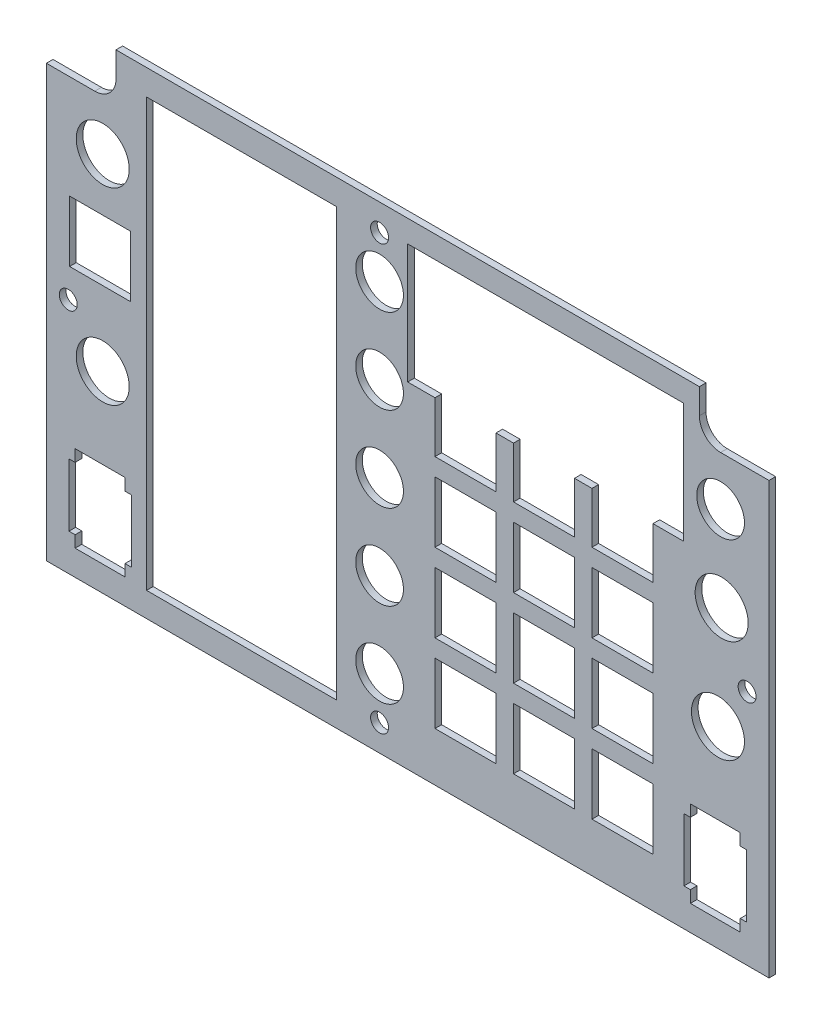
SolidWorks part; units mm, degrees
material "ABS PC"
ref_plane "Front Plane" through (0, 0, 0) normal (0, 0, 1) x (1, 0, 0)
ref_plane "Top Plane" through (0, 0, 0) normal (0, 1, 0) x (1, 0, 0)
ref_plane "Right Plane" through (0, 0, 0) normal (1, 0, 0) x (0, 0, -1)
sketch "Sketch1" plane through (0, 0, 0) normal (0, 0, 1) x (1, 0, 0)
  line L8 (58.2068, 169.534) -> (58.2068, 175.5665)
  line L9 (58.2068, 175.5665) -> (-81.4932, 175.5665)
  line L10 (-81.4932, 175.5665) -> (-81.4932, 169.534)
  line L11 (-86.5732, 164.454) -> (-98.162, 164.454)
  line L12 (-98.162, 164.454) -> (-98.162, 61.2665)
  line L13 (-98.162, 61.2665) -> (74.8755, 61.2665)
  line L14 (74.8755, 61.2665) -> (74.8755, 164.454)
  line L15 (74.8755, 164.454) -> (63.2868, 164.454)
  line L16 (58.2068, 169.534) -> (58.2068, 175.5665)
  line L17 (58.2068, 175.5665) -> (-81.4932, 175.5665)
  line L18 (-81.4932, 175.5665) -> (-81.4932, 169.534)
  line L19 (-86.5732, 164.454) -> (-98.162, 164.454)
  line L20 (-98.162, 164.454) -> (-98.162, 61.2665)
  line L21 (-98.162, 61.2665) -> (74.8755, 61.2665)
  line L22 (74.8755, 61.2665) -> (74.8755, 164.454)
  line L23 (74.8755, 164.454) -> (63.2868, 164.454)
  arc A2 (58.2068, 169.534) -> (63.2868, 164.454) centre (63.2868, 169.534) ccw
  arc A3 (-86.5732, 164.454) -> (-81.4932, 169.534) centre (-86.5732, 169.534) ccw
  arc A4 (58.2068, 169.534) -> (63.2868, 164.454) centre (63.2868, 169.534) ccw
  arc A5 (-86.5732, 164.454) -> (-81.4932, 169.534) centre (-86.5732, 169.534) ccw
  dimension "D1" = 0
extrude "Boss-Extrude1" add sketch "Sketch1" along normal blind 1.5875
sketch "Sketch2" plane through (0, 0, 1.5875) normal (0, 0, 1) x (1, 0, 0)
  line L4 (67.9868, 85.1738) -> (67.9868, 87.9695)
  line L5 (56.0468, 67.3295) -> (67.9868, 67.3295)
  line L6 (56.0468, 70.1738) -> (56.0468, 67.3295)
  line L7 (67.9868, 87.9695) -> (56.0468, 87.9695)
  line L8 (67.9868, 85.1738) -> (67.9868, 87.9695)
  line L9 (56.0468, 67.3295) -> (67.9868, 67.3295)
  line L10 (56.0468, 70.1738) -> (56.0468, 67.3295)
  line L11 (67.9868, 87.9695) -> (56.0468, 87.9695)
  line L26 (32.4893, 73.014) -> (47.0943, 73.014)
  line L27 (32.4893, 87.619) -> (32.4893, 73.014)
  line L28 (47.0943, 87.619) -> (32.4893, 87.619)
  line L29 (47.0943, 73.014) -> (47.0943, 87.619)
  line L30 (32.4893, 73.014) -> (47.0943, 73.014)
  line L31 (32.4893, 87.619) -> (32.4893, 73.014)
  line L32 (47.0943, 87.619) -> (32.4893, 87.619)
  line L33 (47.0943, 73.014) -> (47.0943, 87.619)
  line L34 (32.4893, 91.81) -> (47.0943, 91.81)
  line L35 (32.4893, 106.415) -> (32.4893, 91.81)
  line L36 (47.0943, 106.415) -> (32.4893, 106.415)
  line L37 (47.0943, 91.81) -> (47.0943, 106.415)
  line L38 (32.4893, 91.81) -> (47.0943, 91.81)
  line L39 (32.4893, 106.415) -> (32.4893, 91.81)
  line L40 (47.0943, 106.415) -> (32.4893, 106.415)
  line L41 (47.0943, 91.81) -> (47.0943, 106.415)
  line L42 (32.4893, 110.606) -> (47.0943, 110.606)
  line L43 (32.4893, 125.211) -> (32.4893, 110.606)
  line L44 (47.0943, 125.211) -> (32.4893, 125.211)
  line L45 (47.0943, 110.606) -> (47.0943, 125.211)
  line L46 (32.4893, 110.606) -> (47.0943, 110.606)
  line L47 (32.4893, 125.211) -> (32.4893, 110.606)
  line L48 (47.0943, 125.211) -> (32.4893, 125.211)
  line L49 (47.0943, 110.606) -> (47.0943, 125.211)
  line L51 (13.6933, 73.014) -> (28.2983, 73.014)
  line L52 (13.6933, 87.619) -> (13.6933, 73.014)
  line L53 (28.2983, 87.619) -> (13.6933, 87.619)
  line L54 (28.2983, 73.014) -> (28.2983, 87.619)
  line L55 (13.6933, 73.014) -> (28.2983, 73.014)
  line L56 (13.6933, 87.619) -> (13.6933, 73.014)
  line L57 (28.2983, 87.619) -> (13.6933, 87.619)
  line L58 (28.2983, 73.014) -> (28.2983, 87.619)
  line L59 (13.6933, 91.81) -> (28.2983, 91.81)
  line L60 (13.6933, 106.415) -> (13.6933, 91.81)
  line L61 (28.2983, 106.415) -> (13.6933, 106.415)
  line L62 (32.4893, 141.6095) -> (32.4893, 129.402)
  line L63 (28.2983, 141.6095) -> (32.4893, 141.6095)
  line L64 (28.2983, 129.402) -> (28.2983, 141.6095)
  line L65 (13.6933, 129.402) -> (28.2983, 129.402)
  line L66 (13.6933, 141.6095) -> (13.6933, 129.402)
  line L67 (9.5023, 141.6095) -> (13.6933, 141.6095)
  line L68 (9.5023, 129.402) -> (9.5023, 141.6095)
  line L69 (-5.1027, 129.402) -> (9.5023, 129.402)
  line L70 (-5.1027, 141.6095) -> (-5.1027, 129.402)
  line L71 (-11.6432, 141.6095) -> (-5.1027, 141.6095)
  line L72 (-11.6432, 170.2495) -> (-11.6432, 141.6095)
  line L73 (54.3968, 170.2495) -> (-11.6432, 170.2495)
  line L74 (54.3968, 141.6095) -> (54.3968, 170.2495)
  line L75 (47.0943, 141.6095) -> (54.3968, 141.6095)
  line L76 (47.0943, 129.402) -> (47.0943, 141.6095)
  line L77 (32.4893, 129.402) -> (47.0943, 129.402)
  line L78 (32.4893, 141.6095) -> (32.4893, 129.402)
  line L79 (28.2983, 141.6095) -> (32.4893, 141.6095)
  line L80 (28.2983, 129.402) -> (28.2983, 141.6095)
  line L81 (13.6933, 129.402) -> (28.2983, 129.402)
  line L82 (13.6933, 141.6095) -> (13.6933, 129.402)
  line L83 (9.5023, 141.6095) -> (13.6933, 141.6095)
  line L84 (9.5023, 129.402) -> (9.5023, 141.6095)
  line L85 (-5.1027, 129.402) -> (9.5023, 129.402)
  line L86 (-5.1027, 141.6095) -> (-5.1027, 129.402)
  line L87 (-11.6432, 141.6095) -> (-5.1027, 141.6095)
  line L88 (-11.6432, 170.2495) -> (-11.6432, 141.6095)
  line L89 (54.3968, 170.2495) -> (-11.6432, 170.2495)
  line L90 (54.3968, 141.6095) -> (54.3968, 170.2495)
  line L91 (47.0943, 141.6095) -> (54.3968, 141.6095)
  line L92 (47.0943, 129.402) -> (47.0943, 141.6095)
  line L93 (32.4893, 129.402) -> (47.0943, 129.402)
  line L94 (28.2983, 91.81) -> (28.2983, 106.415)
  line L95 (13.6933, 91.81) -> (28.2983, 91.81)
  line L96 (13.6933, 106.415) -> (13.6933, 91.81)
  line L97 (28.2983, 106.415) -> (13.6933, 106.415)
  line L98 (28.2983, 91.81) -> (28.2983, 106.415)
  line L99 (13.6933, 110.606) -> (28.2983, 110.606)
  line L100 (13.6933, 125.211) -> (13.6933, 110.606)
  line L101 (28.2983, 125.211) -> (13.6933, 125.211)
  line L102 (28.2983, 110.606) -> (28.2983, 125.211)
  line L103 (13.6933, 110.606) -> (28.2983, 110.606)
  line L104 (13.6933, 125.211) -> (13.6933, 110.606)
  line L105 (28.2983, 125.211) -> (13.6933, 125.211)
  line L106 (28.2983, 110.606) -> (28.2983, 125.211)
  line L107 (9.5023, 125.211) -> (-5.1027, 125.211)
  line L108 (9.5023, 110.606) -> (9.5023, 125.211)
  line L109 (-5.1027, 110.606) -> (9.5023, 110.606)
  line L110 (-5.1027, 125.211) -> (-5.1027, 110.606)
  line L111 (9.5023, 125.211) -> (-5.1027, 125.211)
  line L112 (9.5023, 110.606) -> (9.5023, 125.211)
  line L113 (-5.1027, 110.606) -> (9.5023, 110.606)
  line L114 (-5.1027, 125.211) -> (-5.1027, 110.606)
  line L115 (-5.1027, 91.81) -> (9.5023, 91.81)
  line L116 (-5.1027, 106.415) -> (-5.1027, 91.81)
  line L117 (9.5023, 106.415) -> (-5.1027, 106.415)
  line L118 (9.5023, 91.81) -> (9.5023, 106.415)
  line L119 (-5.1027, 91.81) -> (9.5023, 91.81)
  line L120 (-5.1027, 106.415) -> (-5.1027, 91.81)
  line L121 (9.5023, 106.415) -> (-5.1027, 106.415)
  line L122 (9.5023, 91.81) -> (9.5023, 106.415)
  line L123 (-5.1027, 73.014) -> (9.5023, 73.014)
  line L124 (-5.1027, 87.619) -> (-5.1027, 73.014)
  line L125 (9.5023, 87.619) -> (-5.1027, 87.619)
  line L126 (9.5023, 73.014) -> (9.5023, 87.619)
  line L127 (-5.1027, 73.014) -> (9.5023, 73.014)
  line L128 (-5.1027, 87.619) -> (-5.1027, 73.014)
  line L129 (9.5023, 87.619) -> (-5.1027, 87.619)
  line L130 (9.5023, 73.014) -> (9.5023, 87.619)
  line L131 (-78.0007, 139.689) -> (-92.6057, 139.689)
  line L132 (-78.0007, 125.084) -> (-78.0007, 139.689)
  line L133 (-92.6057, 125.084) -> (-78.0007, 125.084)
  line L134 (-92.6057, 139.689) -> (-92.6057, 125.084)
  line L135 (-78.0007, 139.689) -> (-92.6057, 139.689)
  line L136 (-78.0007, 125.084) -> (-78.0007, 139.689)
  line L137 (-92.6057, 125.084) -> (-78.0007, 125.084)
  line L138 (-92.6057, 139.689) -> (-92.6057, 125.084)
  line L139 (-74.1732, 67.1295) -> (-28.7112, 67.1295)
  line L140 (-74.1732, 169.4495) -> (-74.1732, 67.1295)
  line L141 (-28.7112, 169.4495) -> (-74.1732, 169.4495)
  line L142 (-28.7112, 67.1295) -> (-28.7112, 169.4495)
  line L143 (-74.1732, 67.1295) -> (-28.7112, 67.1295)
  line L144 (-74.1732, 169.4495) -> (-74.1732, 67.1295)
  line L145 (-28.7112, 169.4495) -> (-74.1732, 169.4495)
  line L146 (-28.7112, 67.1295) -> (-28.7112, 169.4495)
  line L147 (-79.3332, 85.1165) -> (-79.3332, 87.9695)
  line L148 (-91.2732, 67.3295) -> (-79.3332, 67.3295)
  line L149 (-91.2732, 70.1165) -> (-91.2732, 67.3295)
  line L150 (-79.3332, 87.9695) -> (-91.2732, 87.9695)
  line L151 (-79.3332, 85.1165) -> (-79.3332, 87.9695)
  line L152 (-91.2732, 67.3295) -> (-79.3332, 67.3295)
  line L153 (-91.2732, 70.1165) -> (-91.2732, 67.3295)
  line L154 (-79.3332, 87.9695) -> (-91.2732, 87.9695)
  line L176 (54.505, 85.1738) -> (54.505, 70.1738)
  line L177 (54.505, 85.1738) -> (54.505, 70.1738)
  line L178 (56.0468, 85.1738) -> (54.505, 85.1738)
  line L179 (56.0468, 85.1738) -> (54.505, 85.1738)
  line L180 (56.0468, 87.9695) -> (56.0468, 85.1738)
  line L181 (56.0468, 87.9695) -> (56.0468, 85.1738)
  line L182 (69.505, 85.1738) -> (67.9868, 85.1738)
  line L183 (69.505, 85.1738) -> (67.9868, 85.1738)
  line L184 (69.505, 70.1738) -> (69.505, 85.1738)
  line L185 (69.505, 70.1738) -> (69.505, 85.1738)
  line L186 (67.9868, 70.1738) -> (69.505, 70.1738)
  line L187 (67.9868, 70.1738) -> (69.505, 70.1738)
  line L188 (67.9868, 67.3295) -> (67.9868, 70.1738)
  line L189 (67.9868, 67.3295) -> (67.9868, 70.1738)
  line L190 (54.505, 70.1738) -> (56.0468, 70.1738)
  line L191 (54.505, 70.1738) -> (56.0468, 70.1738)
  line L192 (-92.7558, 85.1165) -> (-92.7558, 70.1165)
  line L193 (-92.7558, 85.1165) -> (-92.7558, 70.1165)
  line L194 (-91.2732, 85.1165) -> (-92.7558, 85.1165)
  line L195 (-91.2732, 85.1165) -> (-92.7558, 85.1165)
  line L196 (-91.2732, 87.9695) -> (-91.2732, 85.1165)
  line L197 (-91.2732, 87.9695) -> (-91.2732, 85.1165)
  line L198 (-77.7558, 85.1165) -> (-79.3332, 85.1165)
  line L199 (-77.7558, 85.1165) -> (-79.3332, 85.1165)
  line L200 (-77.7558, 70.1165) -> (-77.7558, 85.1165)
  line L201 (-77.7558, 70.1165) -> (-77.7558, 85.1165)
  line L202 (-79.3332, 70.1165) -> (-77.7558, 70.1165)
  line L203 (-79.3332, 70.1165) -> (-77.7558, 70.1165)
  line L204 (-79.3332, 67.3295) -> (-79.3332, 70.1165)
  line L205 (-79.3332, 67.3295) -> (-79.3332, 70.1165)
  line L206 (-92.7558, 70.1165) -> (-91.2732, 70.1165)
  line L207 (-92.7558, 70.1165) -> (-91.2732, 70.1165)
  circle A0 centre (-84.6682, 152.389) radius 6.35
  circle A1 centre (-84.6682, 107.304) radius 6.35
  circle A2 centre (63.5408, 132.3865) radius 6.35
  circle A3 centre (62.6518, 107.304) radius 6.35
  circle A10 centre (-18.3742, 77.7765) radius 5.715 construction
  circle A11 centre (-18.3742, 98.0965) radius 5.715 construction
  circle A12 centre (-18.3742, 118.4165) radius 5.715 construction
  circle A13 centre (-18.3742, 138.7365) radius 5.715 construction
  circle A14 centre (-18.3742, 159.0565) radius 5.715 construction
  circle A15 centre (-18.3742, 77.7765) radius 5.715
  circle A16 centre (-18.3742, 98.0965) radius 5.715
  circle A17 centre (-18.3742, 118.4165) radius 5.715
  circle A18 centre (-18.3742, 138.7365) radius 5.715
  circle A19 centre (-18.3742, 159.0565) radius 5.715
  circle A20 centre (63.2868, 152.7065) radius 5.715 construction
  circle A21 centre (63.2868, 152.7065) radius 5.715
  dimension "D1" = 12.7
  dimension "D2" = 0
  dimension "D3" = 0
  dimension "D4" = 0
  dimension "D5" = 0
  dimension "D6" = 0
  dimension "D7" = 0
  dimension "D8" = 0
  dimension "D9" = 0
  dimension "D10" = 0
  dimension "D11" = 0
  dimension "D12" = 0
  dimension "D13" = 0
  dimension "D14" = 0
  dimension "D15" = 0
extrude "Cut-Extrude1" cut sketch "Sketch2" against normal through all
hole_wizard "#6 Clearance Hole2" positions "Sketch5" profile "Sketch6" hole size "#6" standard "ANSI Inch" end condition through all
sketch "Sketch5" plane through (-11.6432, -6.6627, -3.175) normal (0, 0, -1) x (-1, 0, 0)
  point P0 (-81.28, 124.6982)
  point P3 (6.731, 175.8792)
  point P6 (81.28, 124.6982)
  point P9 (6.731, 74.2792)
sketch "Sketch6" plane through (69.6368, 118.0355, -3.175) normal (1, 0, 0) x (0, 1, 0)
  line L0 (0, 0) -> (0, 4.7625)
  line L1 (0, 4.7625) -> (2.1526, 4.7625)
  line L2 (2.1526, 4.7625) -> (2.1526, 0)
  line L3 (2.1526, 0) -> (0, 0)
  line L4 (0, -6.35) -> (0, 107.95) construction
  dimension "Thru Hole Dia." = 4.3053
  dimension "Thru Hole Depth" = 4.7625
sketch "Sketch7" plane through (0, 0, 1.5875) normal (0, 0, 1) x (1, 0, 0)
  line L0 (62.005, 85.1738) -> (62.005, 70.1738) construction
  line L1 (54.505, 85.1738) -> (69.505, 85.1738)
  line L2 (54.505, 85.1738) -> (54.505, 70.1738)
  line L3 (54.505, 70.1738) -> (69.505, 70.1738)
  line L4 (69.505, 85.1738) -> (69.505, 70.1738)
  line L5 (-77.7558, 70.1165) -> (-92.7558, 70.1165)
  line L6 (-77.7558, 70.1165) -> (-77.7558, 85.1165)
  line L7 (-77.7558, 85.1165) -> (-92.7558, 85.1165)
  line L8 (-92.7558, 70.1165) -> (-92.7558, 85.1165)
  line L9 (-85.2558, 85.1165) -> (-85.2558, 70.1165) construction
  point P10 (62.005, 77.6738)
  point P13 (-85.2558, 77.6165)
  dimension "D1" = 15
extrude "Cut-Extrude2" [suppressed] cut sketch "Sketch7" against normal up to next
